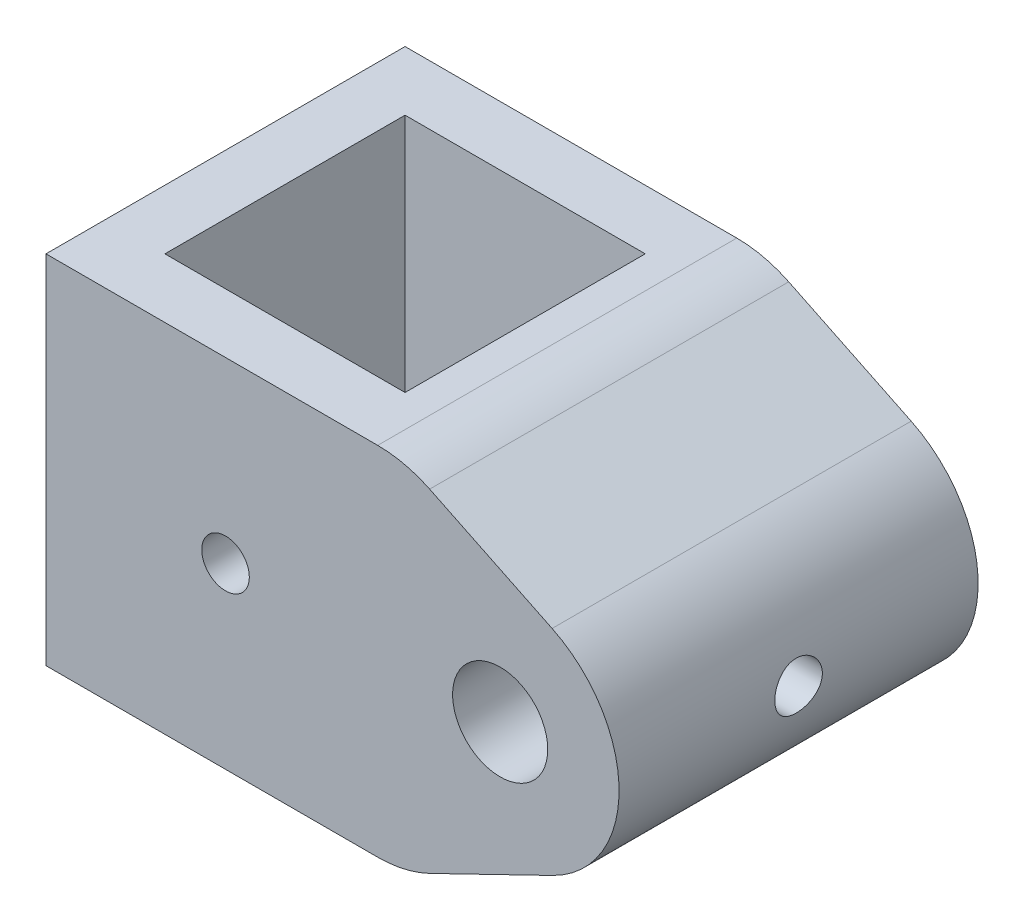
SolidWorks part; units mm, degrees
ref_plane "Front Plane" through (0, 0, 0) normal (0, 0, 1) x (1, 0, 0)
ref_plane "Top Plane" through (0, 0, 0) normal (0, 1, 0) x (1, 0, 0)
ref_plane "Right Plane" through (0, 0, 0) normal (1, 0, 0) x (0, 0, -1)
sketch "Sketch1" plane through (0, 0, 0) normal (0, 1, 0) x (1, 0, 0)
  line L1 (0, 0) -> (20.2, 0)
  line L2 (0, 0) -> (0, 20.2)
  line L3 (0, 20.2) -> (20.2, 20.2)
  line L4 (20.2, 0) -> (20.2, 20.2)
  dimension "D1" = 20.2
extrude "Extrude-Thin1" add sketch "Sketch1" along normal blind 30 thin thin type one direction wall 5
sketch "Sketch2" plane through (0, 0, 5) normal (0, 0, 1) x (1, 0, 0)
  line L0 (25.2, 30) -> (37.5673, 23.9959)
  line L1 (25.2, 30) -> (25.2, 0) construction
  line L2 (37.5673, 6.0041) -> (25.2, 0)
  line L3 (33.2, 15) -> (25.2, 15) construction
  line L4 (-5, 30) -> (25.2, 30) construction
  circle A0 centre (33.2, 15) radius 4
  circle A1 centre (33.2, 15) radius 10
  line M5 (25.2, 0) -> (25.2, 30)
  dimension "D1" = 8
  dimension "D2" = 6
  dimension "D3" = 8
extrude "Boss-Extrude1" add sketch "Sketch2" against normal up to surface (30.2 mm away) contours A0 A1 | L3 A1 L0 M5 | A1 L3 L2 M5 region at (28.298, 25.8893, 5) region at (41.4476, 20.1641, 5) region at (28.298, 4.1107, 5) up to face at (10.1, 15, -25.2)
fillet "Fillet1" radius 10 2 edges at (25.2, 0, -10.1) (25.2, 30, -10.1)
sketch "Sketch3" plane through (0, 0, 5) normal (0, 0, 1) x (1, 0, 0)
  line L1 (0, 30) -> (20.2, 30)
  line L2 (-5, 30) -> (-5, 0) construction
  line L3 (0, 30) -> (20.2, 30) construction
  line L4 (-5, 30) -> (22.9009, 30) construction
  circle A0 centre (10.1, 15) radius 2
  point P2 (0, 0)
  point P5 (0, 0)
  point P6 (10.1, 30)
  point P9 (-5, 15)
  point P12 (4.1298, 15)
  point P13 (15.4237, 30)
  point P16 (-2.1513, 30)
  point P18 (0, 0)
  dimension "D1" = 4
extrude "Cut-Extrude1" cut sketch "Sketch3" against normal through all contours A0
ref_plane "Plane1" through (43.2, 0, 0) normal (1, 0, 0) x (0, 0, -1)
sketch "Sketch4" plane through (43.2, 0, 0) normal (1, 0, 0) x (0, 0, -1)
  line L0 (-5, 15) -> (25.2, 15) construction
  line L1 (-5, 23.9959) -> (-5, 6.0041) construction
  line L2 (25.2, 6.0041) -> (25.2, 23.9959) construction
  circle A0 centre (10.1, 15) radius 2
  point P8 (8.0376, 12.4101)
  point P9 (10.1, 15)
  dimension "D1" = 4
extrude "Cut-Extrude2" cut sketch "Sketch4" against normal up to next
